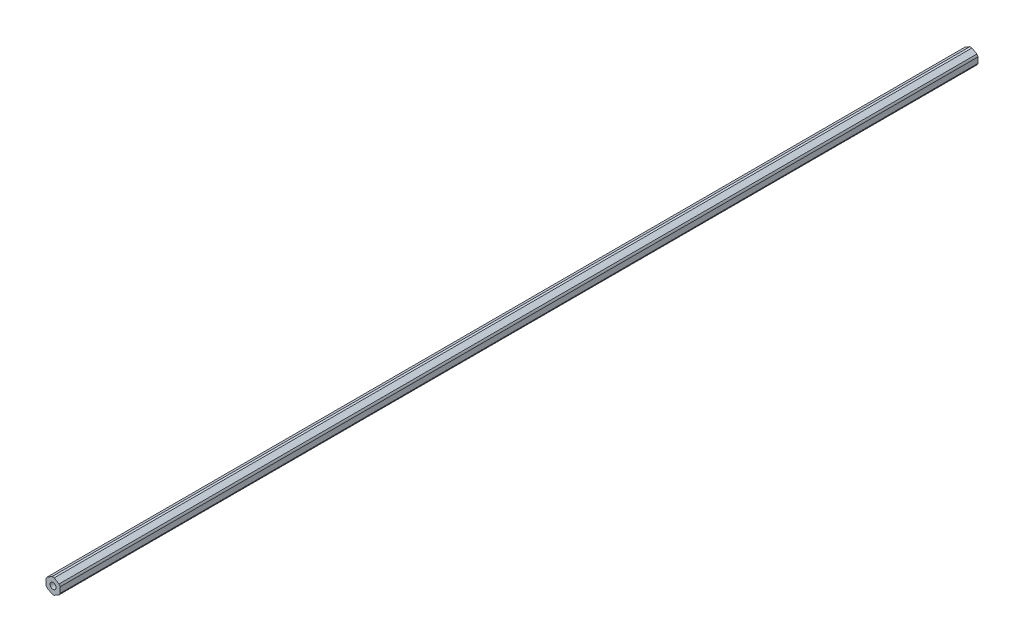
SolidWorks part; units mm, degrees
material "7075-T6 (SN)"
ref_plane "Front Plane" through (0, 0, 0) normal (0, 0, 1) x (1, 0, 0)
ref_plane "Top Plane" through (0, 0, 0) normal (0, 1, 0) x (1, 0, 0)
ref_plane "Right Plane" through (0, 0, 0) normal (1, 0, 0) x (0, 0, -1)
sketch "Sketch2" plane through (0, 0, 0) normal (0, 0, 1) x (1, 0, 0)
  line L1 (0, 5.4993) -> (-4.7625, 2.7496)
  line L2 (-4.7625, 2.7496) -> (-4.7625, -2.7496)
  line L3 (-4.7625, -2.7496) -> (0, -5.4993)
  line L4 (0, -5.4993) -> (4.7625, -2.7496)
  line L5 (4.7625, -2.7496) -> (4.7625, 2.7496)
  line L6 (4.7625, 2.7496) -> (0, 5.4993)
  circle A0 centre (0, 0) radius 4.7625 construction
  circle A2 centre (0, 0) radius 2.0193
  circle A3 centre (0, 0) radius 5.125
  dimension "D1" = 9.525
  dimension "D2" = 10.25
  dimension "D3" = 4.0386
extrude "Boss-Extrude1" add sketch "Sketch2" along normal mid plane 615.95 contours L5 A3 L6 L1 L2 L3 L4 A2 region at (0, 4.9851, 0)
hole_wizard "#10-32 Tapped Hole2" positions "3DSketch1" profile "Sketch6" tap size "#10-32" standard "ANSI Inch"
sketch3d "3DSketch1"
  circle A0 centre (0, 0, 307.975) radius 2.0193 construction
  circle A1 centre (0, 0, -307.975) radius 2.0193 construction
  point P0 (0, 0, -307.975)
  point P2 (0, 0, 307.975)
  point P7 (0, 0, 309.9943)
  point P10 (0, 0, -305.9557)
sketch "Sketch6" plane through (0, 0, -307.975) normal (1, 0, 0) x (0, 1, 0)
  line L0 (0, 0) -> (0, 17.5608)
  line L1 (0, 17.5608) -> (2.0193, 16.3474)
  line L2 (2.0193, 16.3474) -> (2.0193, 0)
  line L5 (2.0193, 0) -> (0, 0)
  line L10 (0, 17.5608) -> (-2.0193, 16.3474) construction
  line L11 (0, -6.35) -> (0, 107.95) construction
  dimension "Tap Drill Dia." = 4.0386
  dimension "Tap Drill Depth" = 16.3474
  dimension "Drill Angle" = 118
cosmetic thread "Hole Thread2" parameters "D1"=13.97, "D2"=4.826
cosmetic thread "Hole Thread3" parameters "D1"=13.97, "D2"=4.826
equation "\"D2@Sketch2\"=10.25mm"
